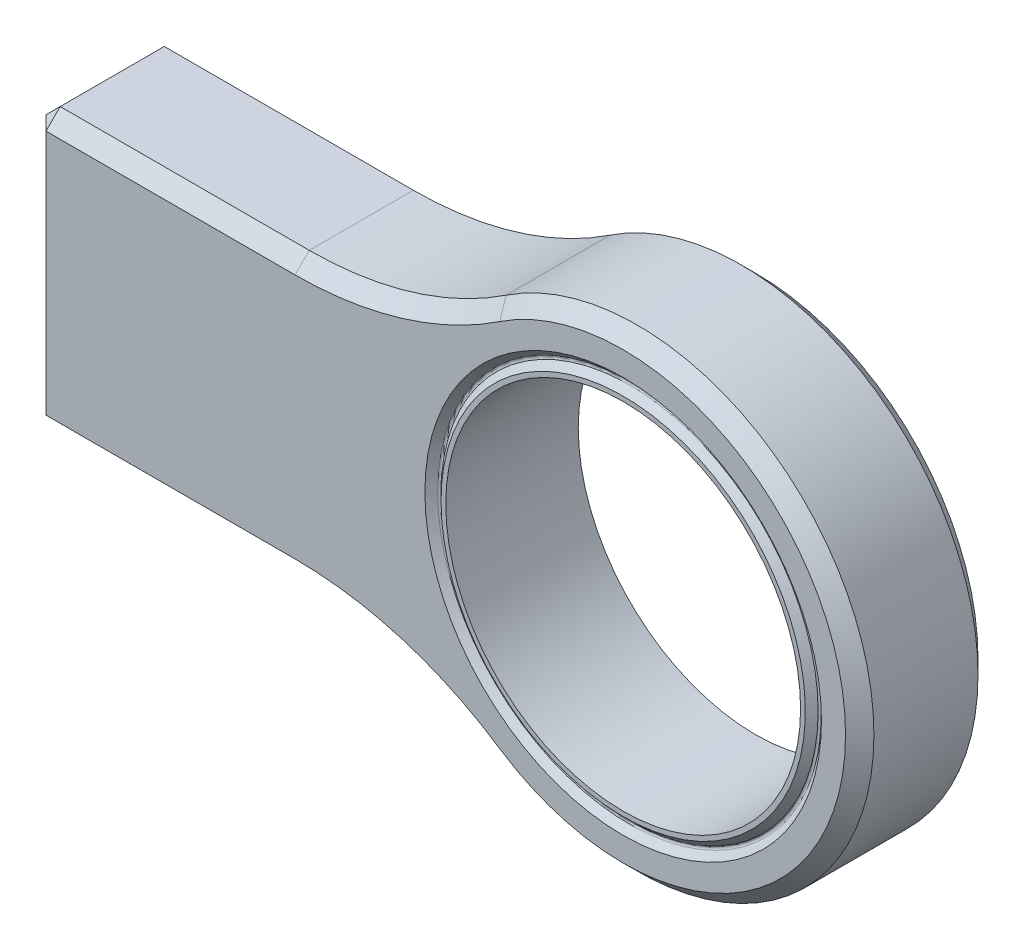
SolidWorks part; units mm, degrees
material "6061 Alloy"
ref_plane "Front Plane" through (0, 0, 0) normal (0, 0, 1) x (1, 0, 0)
ref_plane "Top Plane" through (0, 0, 0) normal (0, 1, 0) x (1, 0, 0)
ref_plane "Right Plane" through (0, 0, 0) normal (1, 0, 0) x (0, 0, -1)
sketch "Sketch1" plane through (0, 0, 0) normal (0, 0, 1) x (1, 0, 0)
  line L7 (-31.75, 7.366) -> (-31.75, -7.366)
  line L8 (-31.75, -7.366) -> (-10.3456, -7.366)
  line L9 (-31.75, 7.366) -> (-10.3456, 7.366)
  line L10 (-54.1585, 0) -> (0, 0) construction
  circle A0 centre (0, 0) radius 9.525
  arc A2 (-10.3456, -7.366) -> (-10.3456, 7.366) centre (0, 0) ccw construction
  arc A3 (-10.3456, -7.366) -> (-10.3456, 7.366) centre (0, 0) ccw
  point P10 (-31.75, 0)
  dimension "D2" = 19.05
  dimension "D1" = 25.4
  dimension "D3" = 14.732
  dimension "D4" = 31.75
extrude "Boss-Extrude1" add sketch "Sketch1" along normal mid plane 7.112
fillet "Fillet1" radius 19.05 2 edges at (-10.3456, 7.366, 0) (-10.3456, -7.366, 0)
chamfer "Chamfer2" distance 0.762 angle 45 14 edges at (-24.6821, 7.366, -3.556) (-24.6821, 7.366, 3.556) (-12.0929, 8.1836, -3.556) (-12.0929, 8.1836, 3.556) (12.7, 0, -3.556) (12.7, 0, 3.556) (-12.0929, -8.1836, -3.556) (-12.0929, -8.1836, 3.556) (-24.6821, -7.366, -3.556) (-31.75, 7.366, 0) (-31.75, 0, -3.556) (-31.75, -7.366, 0) (-31.75, 0, 3.556) (-24.6821, -7.366, 3.556)
ref_axis "Axis1" through (0, 0, -14.1926) along (0, 0, 1)
sketch "Sketch2" plane through (0, 0, 0) normal (0, 1, 0) x (1, 0, 0)
  line L0 (10.6462, 3.556) -> (10.3024, 3.2122)
  line L1 (10.1228, 3.2122) -> (9.779, 3.556)
  line L2 (11.938, 3.556) -> (9.525, 3.556) construction
  line L3 (-30.988, 3.556) -> (-17.6141, 3.556) construction
  line L4 (9.779, 3.556) -> (10.6462, 3.556)
  line L8 (10.2126, 4.2792) -> (10.2126, 2.3992) construction
  arc A0 (10.1228, 3.2122) -> (10.3024, 3.2122) centre (10.2126, 3.302) ccw
  point P17 (10.2126, 3.1224)
  dimension "D4" = 0.127
  dimension "D5" = 0.381
  dimension "D1" = 0.254
  dimension "D2" = 90
  dimension "D3" = 45
revolve "Cut-Revolve1" cut sketch "Sketch2" angle 360 about axis through (0, 0, -14.1926) along (0, 0, 1)
mirror "Mirror1" about plane through (0, 0, 0) normal (0, 0, 1) of "Cut-Revolve1"
ref_point "Point2"
ref_axis "Axis2" through (-33.9725, 0, 0) along (1, 0, 0)
